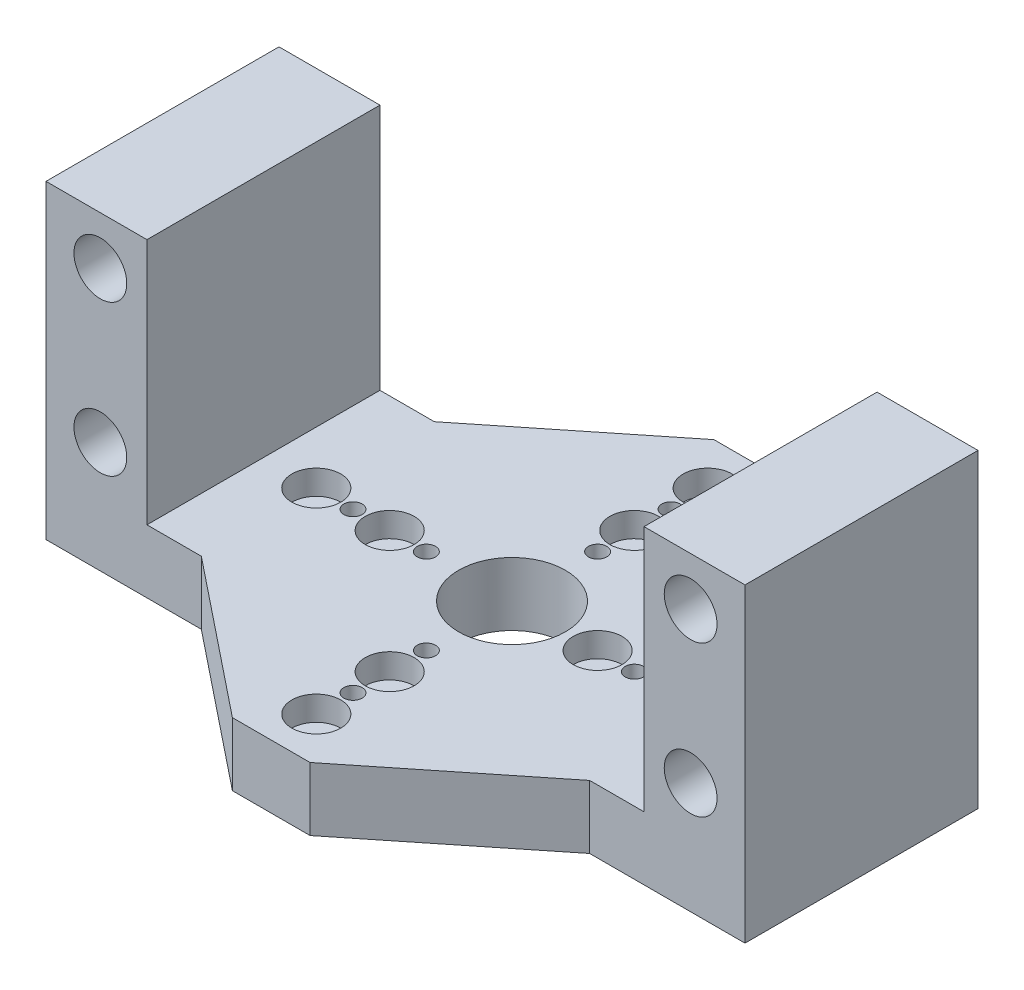
SolidWorks part; units mm, degrees
ref_plane "Front" through (0, 0, 0) normal (0, 0, 1) x (1, 0, 0)
ref_plane "Top" through (0, 0, 0) normal (0, 1, 0) x (1, 0, 0)
ref_plane "Right" through (0, 0, 0) normal (1, 0, 0) x (0, 0, -1)
sketch "Sketch1" plane through (0, 0, 0) normal (0, 0, 1) x (1, 0, 0)
  line L0 (8.255, 25.368) -> (8.255, 5.175)
  line L1 (0, 0) -> (57.15, 0)
  line L2 (0, 0) -> (0, 25.368)
  line L3 (0, 25.368) -> (8.255, 25.368)
  line L4 (57.15, 0) -> (57.15, 25.368)
  line L5 (8.255, 5.175) -> (48.895, 5.175)
  line L6 (48.895, 5.175) -> (48.895, 25.368)
  line L7 (48.895, 25.368) -> (57.15, 25.368)
  line L8 (28.575, 5.175) -> (28.575, 0) construction
  circle A0 centre (4.445, 21.431) radius 2.159
  circle A1 centre (4.445, 9.112) radius 2.159
  circle A2 centre (52.705, 9.112) radius 2.159
  circle A3 centre (52.705, 21.431) radius 2.159
  dimension "D5" = 3.937
  dimension "D6" = 4.318
  dimension "D8" = 3.937
  dimension "D1" = 8.255
  dimension "D2" = 40.64
  dimension "D3" = 5.175
  dimension "D4" = 20.193
  dimension "D7" = 3.81
extrude "Boss-Extrude1" add sketch "Sketch1" along normal blind 19.05
sketch "Sketch2" plane through (0, 0, 0) normal (0, -1, 0) x (1, 0, 0)
  line L0 (28.575, 19.05) -> (28.575, 0) construction
  line L1 (0, 19.05) -> (57.15, 19.05) construction
  line L2 (0, 0) -> (57.15, 0) construction
  line L3 (57.15, 9.525) -> (0, 9.525) construction
  line L4 (57.15, 19.05) -> (57.15, 0) construction
  line L5 (0, 19.05) -> (0, 0) construction
  circle A0 centre (35.575, 9.525) radius 0.75
  circle A1 centre (38.575, 9.525) radius 0.75
  circle A2 centre (41.575, 9.525) radius 0.75
  circle A3 centre (44.575, 9.525) radius 0.75
  circle A4 centre (28.575, 2.525) radius 0.75
  circle A5 centre (28.575, -0.475) radius 0.75
  circle A6 centre (28.575, -3.475) radius 0.75
  circle A7 centre (28.575, -6.475) radius 0.75
  circle A8 centre (21.575, 9.525) radius 0.75
  circle A9 centre (18.575, 9.525) radius 0.75
  circle A10 centre (15.575, 9.525) radius 0.75
  circle A11 centre (12.575, 9.525) radius 0.75
  circle A12 centre (28.575, 16.525) radius 0.75
  circle A13 centre (28.575, 19.525) radius 0.75
  circle A14 centre (28.575, 22.525) radius 0.75
  circle A15 centre (28.575, 25.525) radius 0.75
  circle A16 centre (28.575, 9.525) radius 4.3656
  point P47 (28.575, 9.525)
  dimension "D5" = 1.5
  dimension "D7" = 8.7312
  dimension "D1" = 7
  dimension "D2" = 10
  dimension "D3" = 13
  dimension "D4" = 16
  dimension "D6" = 4
sketch "Sketch3" plane through (0, 0, 0) normal (0, -1, 0) x (1, 0, 0)
  line L0 (0, 19.05) -> (57.15, 19.05) construction
  line L1 (25.4, 19.05) -> (31.75, 19.05) construction
  line L2 (25.4, 19.05) -> (25.4, 29.21) construction
  line L3 (25.4, 29.21) -> (31.75, 29.21)
  line L4 (31.75, 19.05) -> (31.75, 29.21) construction
  line L5 (25.4, 29.21) -> (12.7, 19.05)
  line L6 (31.75, 29.21) -> (44.45, 19.05)
  line L7 (0, 9.525) -> (57.15, 9.525) construction
  line L8 (31.75, -10.16) -> (44.45, 0)
  line L9 (25.4, -10.16) -> (12.7, 0)
  line L10 (25.4, -10.16) -> (31.75, -10.16)
  line L11 (12.7, 19.05) -> (12.7, 0)
  line L12 (44.45, 19.05) -> (44.45, 0)
  point P11 (28.575, 19.05)
  point P12 (28.575, 29.21)
  dimension "D1" = 6.35
  dimension "D2" = 10.16
  dimension "D3" = 12.7
extrude "Boss-Extrude2" add sketch "Sketch3" against normal up to surface (5.175 mm away) up to face at (28.575, 5.175, 9.525)
extrude "Cut-Extrude1" cut sketch "Sketch2" against normal up to surface (5.175 mm away) up to face at (28.575, 5.175, 9.525)
sketch "Sketch4" plane through (0, 5.175, 0) normal (0, 1, 0) x (1, 0, 0)
  circle A0 centre (28.575, 0.475) radius 2
  circle A2 centre (28.575, 6.475) radius 2
  circle A3 centre (12.575, -9.525) radius 2
  circle A4 centre (18.575, -9.525) radius 2
  circle A6 centre (35.575, -9.525) radius 2
  circle A11 centre (28.575, -19.525) radius 2
  circle A12 centre (44.575, -9.525) radius 2
  circle A13 centre (28.575, -25.525) radius 2
  dimension "D1" = 4
extrude "Cut-Extrude2" cut sketch "Sketch4" against normal blind 2
